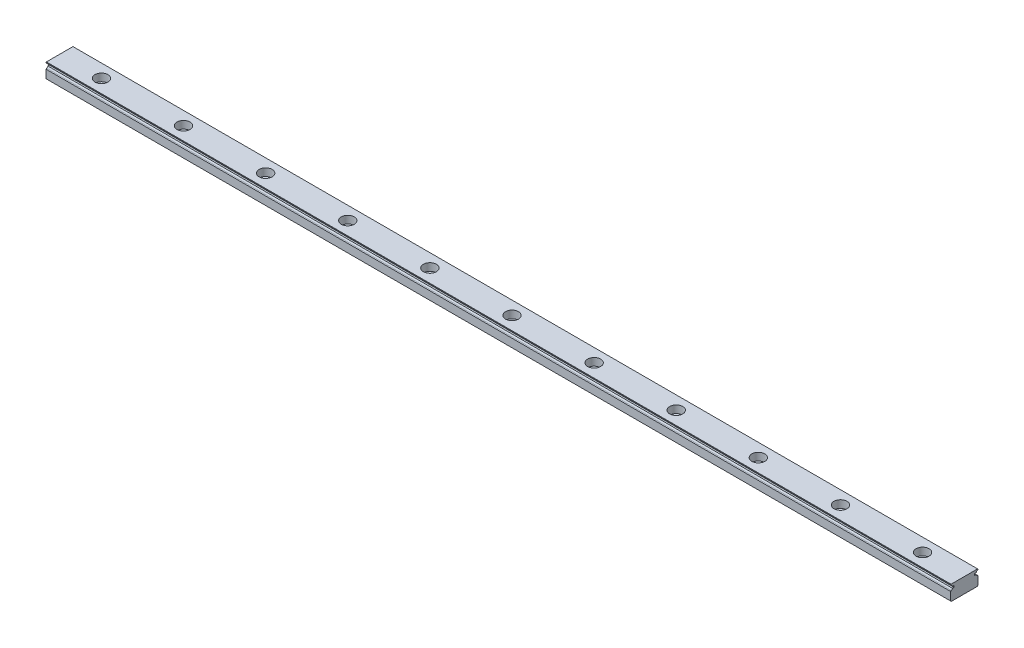
SolidWorks part; units mm, degrees
note: '?' marks a value the reader was unsure of.
ref_plane "Front Plane" through (0, 0, 0) normal (0, 0, 1) x (1, 0, 0)
ref_plane "Top Plane" through (0, 0, 0) normal (0, 1, 0) x (1, 0, 0)
ref_plane "Right Plane" through (0, 0, 0) normal (1, 0, 0) x (0, 0, -1)
ref_axis "Axis_X" through (-9.25, 0, 0) along (1, 0, 0)?
ref_plane "Dim.MC" through (4, 0, 0) normal (1, 0, 0) x (0, 0, -1)
ref_plane "Plane1" through (-30.5, 0, 0) normal (1, 0, 0) x (0, 0, -1)
sketch "Sketch1" plane through (-30.5, 0, 0) normal (1, 0, 0) x (0, 0, -1)
  line L0 (0, 11) -> (0, 0) construction
  line L1 (-10, 11) -> (10, 11)
  line L3 (-10, 0) -> (10, 0)
  line L10 (10, 11) -> (10, 0)
  line L11 (-10, 11) -> (-10, 0)
  dimension "H1" = 11
  dimension "W1" = 20
extrude "Boss-Extrude1" add sketch "Sketch1" along normal blind 661
sketch "Sketch2" plane through (-30.5, 0, 0) normal (1, 0, 0) x (0, 0, -1)
  line L0 (7.5, 8.5) -> (10, 8.5) construction
  line L1 (0, 0) -> (0, 9.1) construction
  line L2 (10, 10.451) -> (9.4553, 10.1414)
  line L3 (7.5, 9.1) -> (8.6371, 9.1)
  line L4 (7.5, 9.1) -> (7.5, 7.9)
  line L5 (7.5, 7.9) -> (8.64, 7.9)
  line L6 (9.4348, 6.8804) -> (10, 6.549)
  line L7 (0, 11) -> (0, 0) construction
  line L8 (10, 10.451) -> (10, 6.549)
  line L9 (10, 11) -> (10, 0) construction
  line L10 (-10, 0) -> (10, 0) construction
  line L11 (-7.5, 8.5) -> (-10, 8.5) construction
  line L12 (-10, 10.451) -> (-10, 6.549)
  line L13 (-9.4348, 6.8804) -> (-10, 6.549)
  line L14 (-7.5, 7.9) -> (-8.64, 7.9)
  line L15 (-7.5, 9.1) -> (-7.5, 7.9)
  line L16 (-7.5, 9.1) -> (-8.6371, 9.1)
  line L17 (-10, 10.451) -> (-9.4553, 10.1414)
  arc A0 (9.4553, 10.1414) -> (8.6371, 9.1) centre (10.32, 8.62) ccw
  arc A1 (8.64, 7.9) -> (9.4348, 6.8804) centre (10.32, 8.39) ccw
  arc A2 (-8.64, 7.9) -> (-9.4348, 6.8804) centre (-10.32, 8.39) cw
  arc A3 (-9.4553, 10.1414) -> (-8.6371, 9.1) centre (-10.32, 8.62) cw
  dimension "MSM_8" = 1.75
  dimension "MSM_6" = 8.5
  dimension "MSM_7" = 60
  dimension "MSM_2" = 0.32
  dimension "MSM_5" = 1.2
  dimension "MSM_1" = 2.5
  dimension "MSM_3" = 8.39
  dimension "MSM_4" = 8.62
extrude "Cut-Extrude1" [suppressed] cut sketch "Sketch2" along normal through all
sketch "Sketch3" plane through (-30.5, 0, 0) normal (1, 0, 0) x (0, 0, -1)
  line L0 (7.5, 8.5) -> (10, 8.5) construction
  line L1 (0, 0) -> (0, 9.1) construction
  line L2 (10, 10.451) -> (9.4553, 10.1414)
  line L3 (7.5, 9.1) -> (8.6371, 9.1)
  line L4 (7.5, 9.1) -> (7.5, 7.9)
  line L5 (7.5, 7.9) -> (8.64, 7.9)
  line L6 (10, 6.549) -> (9.4348, 6.8804)
  line L7 (10, 11) -> (10, 0) construction
  line L8 (10, 10.451) -> (10, 6.549)
  line L9 (-10, 0) -> (10, 0) construction
  line L10 (-7.5, 8.5) -> (-10, 8.5) construction
  line L11 (-10, 10.451) -> (-10, 6.549)
  line L12 (-10, 6.549) -> (-9.4348, 6.8804)
  line L13 (-7.5, 7.9) -> (-8.64, 7.9)
  line L14 (-7.5, 9.1) -> (-7.5, 7.9)
  line L15 (-7.5, 9.1) -> (-8.6371, 9.1)
  line L16 (-10, 10.451) -> (-9.4553, 10.1414)
  arc A0 (9.4553, 10.1414) -> (8.6371, 9.1) centre (10.32, 8.62) ccw
  arc A1 (8.64, 7.9) -> (9.4348, 6.8804) centre (10.32, 8.39) ccw
  arc A2 (-8.64, 7.9) -> (-9.4348, 6.8804) centre (-10.32, 8.39) cw
  arc A3 (-9.4553, 10.1414) -> (-8.6371, 9.1) centre (-10.32, 8.62) cw
  dimension "MSM_8" = 1.75
  dimension "MSM_6" = 8.5
  dimension "MSM_7" = 60
  dimension "MSM_2" = 0.32
  dimension "MSM_5" = 1.2
  dimension "MSM_1" = 2.5
  dimension "MSM_3" = 8.39
  dimension "MSM_4" = 8.62
extrude "Cut-Extrude2" cut sketch "Sketch3" along normal through all
hole_wizard "CBORE for Socket Head Cap Screw1" positions "Sketch5" profile "Sketch4" counterbore size "M3" standard "JIS" end condition through all
sketch "Sketch5" plane through (0, 11, 0) normal (0, 1, 0) x (1, 0, 0)
  line L0 (-30.5, -3.025) -> (-30.5, 3.025) construction
  point P0 (0, 0)
  dimension "G" = 30.5
sketch "Sketch4" plane through (0, 11, 0) normal (1, 0, 0) x (0, 0, 1)
  line L0 (0, 0) -> (0, 11)
  line L1 (0, 11) -> (3, 11)
  line L3 (3, 11) -> (3, 5.5)
  line L4 (3, 5.5) -> (4.75, 5.5)
  line L5 (4.75, 5.5) -> (4.75, 0)
  line L7 (4.75, 0) -> (0, 0)
  line L11 (0, 0) -> (0, 11) construction
  dimension "D1_s" = 6
  dimension "Thru Hole Depth" = 11
  dimension "D2_s" = 9.5
  dimension "H_s" = 5.5
pattern_linear "LPattern1" count 11 spacing 60 along (1, 0, 0) of "CBORE for Socket Head Cap Screw1"
chamfer "Chamfer1" distance 0.3 2 edges at (300, 11, 10) (300, 11, -10)
chamfer "Chamfer2" distance 0.5 2 edges at (300, 0, -10) (300, 0, 10)
ref_plane "Plane2" [suppressed] through (0, 5.5, 0) normal (0, 1, 0) x (1, 0, 0)
hole_wizard "Tap1" [suppressed] positions "Sketch7" profile "Sketch6" hole size "M3x0.5" standard "JIS"
sketch "Sketch7" [suppressed] plane through (0, 5.5, 0) normal (0, 1, 0) x (1, 0, 0)
  line L0 (-7.5, -3.025) -> (-7.5, 3.025) construction
  point P0 (0, 0)
  dimension "G" = 30.5
sketch "Sketch6" [suppressed] plane through (0, 5.5, 0) normal (1, 0, 0) x (0, 0, 1)
  line L0 (0, 0) -> (0, 5.5)
  line L1 (0, 5.5) -> (1.621, 5.5)
  line L2 (1.621, 5.5) -> (1.621, 0)
  line L5 (1.621, 0) -> (0, 0)
  line L11 (0, 0) -> (0, 5.5) construction
  dimension "STD_1" = 3.242
  dimension "Thru Hole Depth" = 5.5
pattern_linear "LPattern2" [suppressed]
sketch "Sketch8" [suppressed] plane through (0, 0, 0) normal (0, 0, 1) x (1, 0, 0)
  line L0 (-7.5, -3.025) -> (-7.5, 3.025) construction
  line L1 (-7.5, 5.5) -> (-5, 5.5)
  line L2 (-7.5, 5.5) -> (-7.5, 0)
  line L3 (-7.5, 0) -> (-5, 0)
  line L4 (-5, 5.5) -> (-5, 0)
  line L5 (0, 5.5) -> (0, 0) construction
  dimension "LLC" = 2.5
  dimension "N" = 5
other "Move Face1" [suppressed]
sketch "Sketch9" [suppressed] plane through (0, 0, 0) normal (0, 0, 1) x (1, 0, 0)
  line L0 (-7.5, 5.5) -> (-7.5, 0) construction
  line L1 (25, 5.5) -> (27.5, 5.5)
  line L2 (25, 5.5) -> (25, 0)
  line L3 (25, 0) -> (27.5, 0)
  line L4 (27.5, 5.5) -> (27.5, 0)
  line L5 (-7.5, -3.025) -> (-7.5, 3.025) construction
  line L8 (20, 5.5) -> (20, 0) construction
  dimension "L" = 661
  dimension "RLC" = 2.5
  dimension "N" = 5
  dimension "KSS_1" = 600
other "Move Face2" [suppressed]
equation "\"KSS_1\"= \"F\" * ( \"M\" - 1 )"
